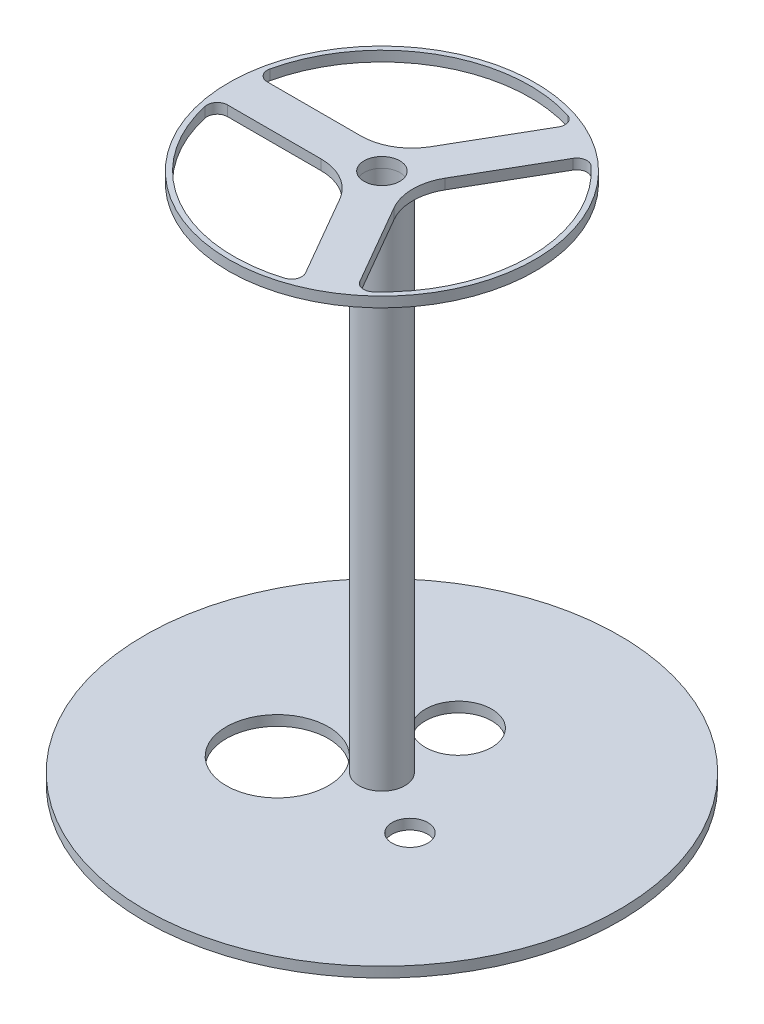
SolidWorks part; units mm, degrees
ref_plane "Front Plane" through (0, 0, 0) normal (0, 0, 1) x (1, 0, 0)
ref_plane "Top Plane" through (0, 0, 0) normal (0, 1, 0) x (1, 0, 0)
ref_plane "Right Plane" through (0, 0, 0) normal (1, 0, 0) x (0, 0, -1)
sketch "Sketch1" plane through (0, 0, 0) normal (0, 1, 0) x (1, 0, 0)
  line L0 (0, 15) -> (0, 0) construction
  line L1 (0, 0) -> (-12.9904, -7.5) construction
  line L2 (0, 0) -> (12.9904, -7.5) construction
  circle A0 centre (0, 0) radius 46.5
  circle A1 centre (0, 15) radius 6.5
  circle A2 centre (-12.9904, -7.5) radius 10
  circle A3 centre (12.9904, -7.5) radius 3.5
  circle A4 centre (0, 0) radius 3.5
  point P3 (0, 15)
  point P8 (12.9904, -7.5)
  point P9 (-12.9904, -7.5)
  point P10 (0, 0)
  dimension "D1" = 93
  dimension "D4" = 13
  dimension "D5" = 20
  dimension "D6" = 7
  dimension "D7" = 7
  dimension "D2" = 15
  dimension "D3" = 3
extrude "Boss-Extrude1" add sketch "Sketch1" along normal blind 2
sketch "Sketch2" plane through (0, 2, 0) normal (0, 1, 0) x (1, 0, 0)
  line L0 (0, 0) -> (12.9904, -7.5) construction
  line L1 (0, 0) -> (0, 46.5) construction
  line L2 (0, 0) -> (-12.9904, -7.5) construction
  line L3 (0, 0) -> (-40.2702, -23.25) construction
  line L4 (0, 0) -> (40.2702, -23.25) construction
  circle A0 centre (0, 0) radius 46.5 construction
  circle A1 centre (-12.9904, -7.5) radius 10 construction
  circle A2 centre (12.9904, -7.5) radius 3.5 construction
  circle A3 centre (0, 0) radius 25
  circle A4 centre (21.6506, -12.5) radius 3
  circle A5 centre (-21.6506, -12.5) radius 3
  circle A6 centre (0, 25) radius 3
  point P22 (0, 0)
  dimension "D1" = 50
  dimension "D2" = 6
  dimension "D3" = 3
sketch "Sketch3" plane through (0, 2, 0) normal (0, 1, 0) x (1, 0, 0)
  circle A0 centre (0, 0) radius 3.5
  circle A1 centre (0, 0) radius 4.5
  dimension "D1" = 9
extrude "Boss-Extrude2" add sketch "Sketch3" along normal blind 100
sketch "Sketch4" plane through (0, 102, 0) normal (0, 1, 0) x (1, 0, 0)
  line L0 (-4.5, 0) -> (-29, 0) construction
  line L11 (-2.25, 3.8971) -> (-28.737, 3.8971)
  line L16 (-2.25, -3.8971) -> (-28.737, -3.8971)
  line L17 (4.5, 0) -> (17.7435, 22.9384)
  line L18 (-2.25, 3.8971) -> (10.9935, 26.8355)
  line L19 (-2.25, -3.8971) -> (10.9935, -26.8355)
  line L20 (4.5, 0) -> (17.7435, -22.9384)
  circle A0 centre (0, 0) radius 30
  circle A1 centre (0, 0) radius 29
  circle A2 centre (0, 0) radius 4.5
  circle A3 centre (0, 0) radius 3.5
  point P21 (0, 0)
  point P23 (0, 0)
  circle M18 centre (0, 0) radius 4.5
  circle M19 centre (0, 0) radius 3.5
  dimension "D1" = 60
  dimension "D2" = 58
  dimension "D4" = 3
extrude "Boss-Extrude5" add sketch "Sketch4" along normal blind 2 separate body contours A0 A1 | L19 A1 L20 M18 | A2 M18 M19 | L17 A1 L18 M18 | L0 L11 A1 M18 | A2 L0 A1 L16 region at (-16.3713, 102, 1.972) region at (-16.3713, 102, -1.972) region at (-3.7869, 102, -2.1864) region at (8.1856, 102, -14.1779) region at (8.1856, 102, 14.1779) region at (-29.1515, 102, 0)
fillet "Fillet1" radius 10 3 edges at (-2.25, 103, -3.8971) (-2.25, 103, 3.8971) (4.5, 103, 0)
fillet "Fillet2" radius 2 6 edges at (17.7435, 103, 22.9384) (17.7435, 103, -22.9384) (10.9935, 103, -26.8355) (-28.737, 103, -3.8971) (-28.737, 103, 3.8971) (10.9935, 103, 26.8355)
sketch "Sketch5" plane through (0, 102, 0) normal (0, -1, 0) x (1, 0, 0)
  line L0 (0, 0) -> (-30, 0) construction
  line L1 (0, 0) -> (15, 25.9808) construction
  line L2 (0, 0) -> (15, -25.9808) construction
  line L3 (7.3868, -5) -> (16.5491, -20.8696) construction
  line L4 (7.3868, 5) -> (16.5491, 20.8696) construction
  line L5 (0.6368, -8.8971) -> (9.7991, -24.7667) construction
  line L6 (8.384, -16.5215) -> (4.884, -10.4593)
  line L7 (8.384, -16.5215) -> (10.116, -15.5215)
  line L8 (10.116, -15.5215) -> (6.616, -9.4593)
  line L9 (4.884, -10.4593) -> (6.616, -9.4593)
  line L10 (8.384, -16.5215) -> (6.616, -9.4593) construction
  line L11 (10.116, -15.5215) -> (4.884, -10.4593) construction
  circle A0 centre (0, 0) radius 15 construction
  circle A1 centre (0, 0) radius 30 construction
  circle A2 centre (-15, 0) radius 1
  circle A3 centre (7.5, 12.9904) radius 3.5
  point P17 (7.5, -12.9904)
  dimension "D1" = 30
  dimension "D2" = 2
  dimension "D3" = 7
  dimension "D4" = 2
  dimension "D5" = 7
extrude "Cut-Extrude1" cut sketch "Sketch5" against normal blind 1
